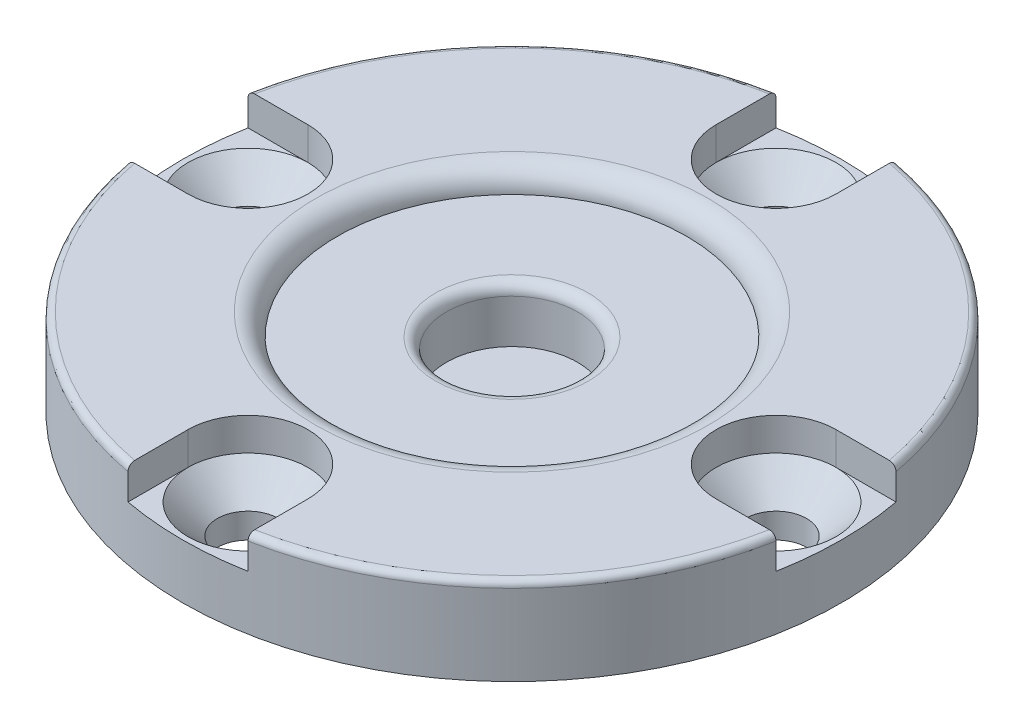
SolidWorks part; units mm, degrees
ref_plane "Front Plane" through (0, 0, 0) normal (0, 0, 1) x (1, 0, 0)
ref_plane "Top Plane" through (0, 0, 0) normal (0, 1, 0) x (1, 0, 0)
ref_plane "Right Plane" through (0, 0, 0) normal (1, 0, 0) x (0, 0, -1)
sketch "Sketch1" plane through (0, 0, 0) normal (0, 1, 0) x (1, 0, 0)
  circle A0 centre (0, 0) radius 15.1
  dimension "D1" = 30.2
extrude "Boss-Extrude1" add sketch "Sketch1" along normal blind 4
sketch "Sketch2" plane through (0, 4, 0) normal (0, 1, 0) x (1, 0, 0)
  line L0 (-2.75, 12.1) -> (-2.75, 14.8475)
  line L1 (2.75, 12.1) -> (2.75, 14.8475)
  line L2 (12.1, -2.75) -> (14.8475, -2.75)
  line L3 (12.1, 2.75) -> (14.8475, 2.75)
  line L4 (-2.75, -12.1) -> (-2.75, -14.8475)
  line L5 (2.75, -12.1) -> (2.75, -14.8475)
  line L6 (-12.1, 2.75) -> (-14.8475, 2.75)
  line L7 (-12.1, -2.75) -> (-14.8475, -2.75)
  circle A0 centre (0, 0) radius 12.1 construction
  arc A1 (-2.75, 12.1) -> (2.75, 12.1) centre (0, 12.1) ccw
  circle A2 centre (0, 0) radius 15.1 construction
  arc A3 (-2.75, 14.8475) -> (2.75, 14.8475) centre (0, 0) cw
  arc A4 (12.1, 2.75) -> (12.1, -2.75) centre (12.1, 0) ccw
  arc A5 (14.8475, 2.75) -> (14.8475, -2.75) centre (0, 0) cw
  arc A6 (2.75, -12.1) -> (-2.75, -12.1) centre (0, -12.1) ccw
  arc A7 (2.75, -14.8475) -> (-2.75, -14.8475) centre (0, 0) cw
  arc A8 (-12.1, -2.75) -> (-12.1, 2.75) centre (-12.1, 0) ccw
  arc A9 (-14.8475, -2.75) -> (-14.8475, 2.75) centre (0, 0) cw
  point P29 (0, 0)
  circle M18 centre (0, 0) radius 15.1
  dimension "D1" = 24.2
  dimension "D2" = 5.5
  dimension "D3" = 4
extrude "Cut-Extrude1" [suppressed] cut sketch "Sketch2" against normal blind 0.55
sketch "Sketch3" [suppressed] plane through (0, 1.45, 0) normal (0, 1, 0) x (1, 0, 0)
  circle A0 centre (0, 12.1) radius 1.4
  circle A1 centre (-12.1, 0) radius 1.4
  circle A2 centre (0, -12.1) radius 1.4
  circle A3 centre (12.1, 0) radius 1.4
  dimension "D1" = 2.8
extrude "Cut-Extrude2" [suppressed] cut sketch "Sketch3" against normal blind 2.55
sketch "Sketch4" plane through (0, 4, 0) normal (0, 1, 0) x (1, 0, 0)
  circle A0 centre (0, 0) radius 8
  dimension "D1" = 16
extrude "Cut-Extrude3" cut sketch "Sketch4" against normal blind 1
sketch "Sketch5" plane through (0, 3, 0) normal (0, 1, 0) x (1, 0, 0)
  circle A0 centre (0, 0) radius 3
  dimension "D1" = 6
extrude "Cut-Extrude4" cut sketch "Sketch5" against normal blind 2.5
fillet "Fillet1" radius 1 1 edges at (0, 4, 8)
fillet "Fillet2" radius 0.5 1 edges at (0, 3, 3)
fillet "Fillet3" radius 0.3 1 edges at (0, 4, 15.1)
extrude "Cut-Extrude5" cut sketch "Sketch2<2>" against normal blind 1.5 contours L7 A8 L6 M18 | L5 A6 L4 M18 | L3 A4 L2 M18 | A1 L1 A3 L0 region at (-12.4416, 4, 0) region at (12.4416, 4, 0) region at (0, 4, 12.4416)
sketch "Sketch2<2>" plane through (0, 4, 0) normal (0, 1, 0) x (1, 0, 0) same geometry as "Sketch2"
hole_wizard "CSK for M2.5 Flat Head Machine Screw1" positions "Sketch6" profile "Sketch7" countersink size "M2.5" standard "ANSI Metric" end condition through all
sketch "Sketch6" plane through (0, 2.5, 0) normal (0, 1, 0) x (1, 0, 0)
  point P0 (0, 12.1)
  point P3 (-12.1, 0)
  point P6 (12.1, 0)
  point P9 (0, -12.1)
sketch "Sketch7" plane through (0, 2.5, -12.1) normal (1, 0, 0) x (0, 0, 1)
  line L0 (0, 0) -> (0, 2.5)
  line L1 (0, 2.5) -> (1.4, 2.5)
  line L2 (1.4, 2.5) -> (1.4, 1.35)
  line L3 (1.4, 1.35) -> (2.75, 0)
  line L5 (2.75, 0) -> (0, 0)
  line L6 (-1.4, 1.35) -> (-2.75, 0) construction
  line L11 (0, -6.35) -> (0, 107.95) construction
  dimension "Thru Hole Dia." = 2.8
  dimension "Thru Hole Depth" = 2.5
  dimension "Near C'Sink Dia." = 5.5
  dimension "Near C'Sink Angle" = 90
